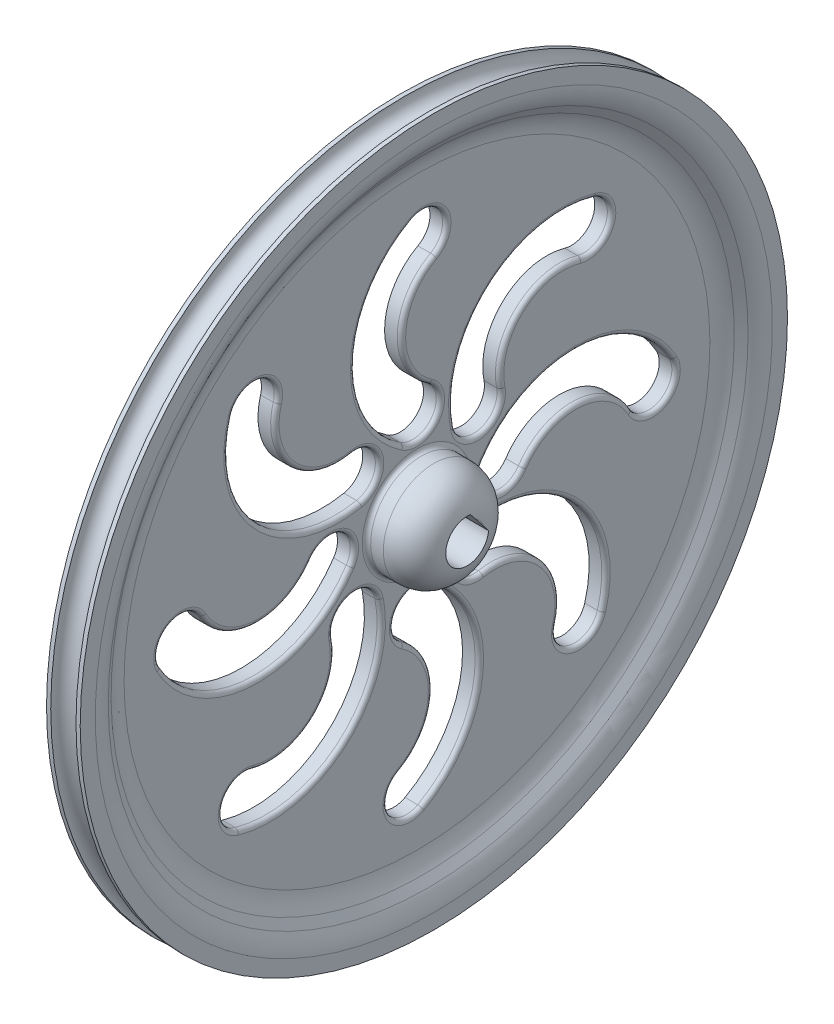
SolidWorks part; units mm, degrees
ref_plane "Płaszczyzna przednia" through (0, 0, 0) normal (0, 0, 1) x (1, 0, 0)
ref_plane "Płaszczyzna górna" through (0, 0, 0) normal (0, 1, 0) x (1, 0, 0)
ref_plane "Płaszczyzna prawa" through (0, 0, 0) normal (1, 0, 0) x (0, 0, -1)
sketch "Szkic1" plane through (0, 0, 0) normal (0, 0, 1) x (1, 0, 0)
  line L0 (6, -12.7789) -> (-2, -12.7789)
  line L1 (6, -12.7789) -> (6, -6.7789)
  line L2 (6, -6.7789) -> (0, -6.7789)
  line L3 (0, -6.7789) -> (0, 22.01)
  line L4 (2, 29.2211) -> (1.5, 29.2211)
  line L5 (2, 29.2211) -> (2, 27.4322)
  line L6 (-1.5, 29.2211) -> (-2, 29.2211)
  line L9 (-2, 29.2211) -> (-2, -12.7789)
  line L10 (0.6718, 24.2288) -> (1.3282, 25.2134)
  arc A0 (1.5, 29.2211) -> (-1.5, 29.2211) centre (0, 29.2211) cw
  arc A1 (2, 27.4322) -> (1.3282, 25.2134) centre (-2, 27.4322) cw
  arc A2 (0, 22.01) -> (0.6718, 24.2288) centre (4, 22.01) cw
  point P10 (2, 26.2211)
  point P17 (0, 23.2211)
  dimension "D6" = 1.5
  dimension "D9" = 4
  dimension "D10" = 4
  dimension "D1" = 8
  dimension "D2" = 6
  dimension "D3" = 42
  dimension "D4" = 4
  dimension "D5" = 3
  dimension "D7" = 0.5
  dimension "D8" = 30
  dimension "D11" = 2
revolve "Obrót1" add sketch "Szkic1" angle 360 about L0
sketch "Szkic4" plane through (6, 0, 0) normal (1, 0, 0) x (0, 0, -1)
  line L0 (0.3809, -10.2575) -> (2.5412, -12.9904)
  arc A0 (0.3809, -10.2575) -> (2.5412, -12.9904) centre (0, -12.7789) ccw
  circle A2 centre (0, -12.7789) radius 6 construction
extrude "Wytnij-wyciągnięcie8" cut sketch "Szkic4" against normal through all
sketch "Szkic5" plane through (0, 0, 0) normal (1, 0, 0) x (0, 0, -1)
  arc A0 (0.7629, 14.985) -> (0, -2.7789) centre (5.766, 5.8718) ccw construction
  arc A1 (-0.5757, 17.4232) -> (-1.5427, -5.0934) centre (5.766, 5.8718) ccw
  arc A2 (2.1015, 12.5467) -> (1.5427, -0.4644) centre (5.766, 5.8718) ccw
  arc A3 (2.1015, 12.5467) -> (-0.5757, 17.4232) centre (0.7629, 14.985) ccw
  arc A4 (-1.5427, -5.0934) -> (1.5427, -0.4644) centre (0, -2.7789) ccw
  circle A5 centre (0, -12.7789) radius 6 construction
  circle A6 centre (0, -12.7789) radius 34.7889 construction
  arc A7 (20.3278, 6.2489) -> (7.2274, -5.7726) centre (17.4216, -3.7328) ccw construction
  arc A8 (21.1053, 8.9195) -> (4.5, -6.3183) centre (17.4216, -3.7328) ccw
  arc A9 (19.5502, 3.5783) -> (9.9548, -5.2269) centre (17.4216, -3.7328) ccw
  arc A10 (19.5502, 3.5783) -> (21.1053, 8.9195) centre (20.3278, 6.2489) ccw
  arc A11 (4.5, -6.3183) -> (9.9548, -5.2269) centre (7.2274, -5.7726) ccw
  arc A12 (27.985, -13.7629) -> (10.2211, -13) centre (18.8718, -18.766) ccw construction
  arc A13 (30.4232, -12.4243) -> (7.9066, -11.4573) centre (18.8718, -18.766) ccw
  arc A14 (25.5467, -15.1015) -> (12.5356, -14.5427) centre (18.8718, -18.766) ccw
  arc A15 (25.5467, -15.1015) -> (30.4232, -12.4243) centre (27.985, -13.7629) ccw
  arc A16 (7.9066, -11.4573) -> (12.5356, -14.5427) centre (10.2211, -13) ccw
  arc A17 (19.2489, -33.3278) -> (7.2274, -20.2274) centre (9.2672, -30.4216) ccw construction
  arc A18 (21.9195, -34.1053) -> (6.6817, -17.5) centre (9.2672, -30.4216) ccw
  arc A19 (16.5783, -32.5502) -> (7.7731, -22.9548) centre (9.2672, -30.4216) ccw
  arc A20 (16.5783, -32.5502) -> (21.9195, -34.1053) centre (19.2489, -33.3278) ccw
  arc A21 (6.6817, -17.5) -> (7.7731, -22.9548) centre (7.2274, -20.2274) ccw
  arc A22 (-0.7629, -40.985) -> (0, -23.2211) centre (-5.766, -31.8718) ccw construction
  arc A23 (0.5757, -43.4232) -> (1.5427, -20.9066) centre (-5.766, -31.8718) ccw
  arc A24 (-2.1015, -38.5467) -> (-1.5427, -25.5356) centre (-5.766, -31.8718) ccw
  arc A25 (-2.1015, -38.5467) -> (0.5757, -43.4232) centre (-0.7629, -40.985) ccw
  arc A26 (1.5427, -20.9066) -> (-1.5427, -25.5356) centre (0, -23.2211) ccw
  arc A27 (-20.3278, -32.2489) -> (-7.2274, -20.2274) centre (-17.4216, -22.2672) ccw construction
  arc A28 (-21.1053, -34.9195) -> (-4.5, -19.6817) centre (-17.4216, -22.2672) ccw
  arc A29 (-19.5502, -29.5783) -> (-9.9548, -20.7731) centre (-17.4216, -22.2672) ccw
  arc A30 (-19.5502, -29.5783) -> (-21.1053, -34.9195) centre (-20.3278, -32.2489) ccw
  arc A31 (-4.5, -19.6817) -> (-9.9548, -20.7731) centre (-7.2274, -20.2274) ccw
  arc A32 (-27.985, -12.2371) -> (-10.2211, -13) centre (-18.8718, -7.234) ccw construction
  arc A33 (-30.4232, -13.5757) -> (-7.9066, -14.5427) centre (-18.8718, -7.234) ccw
  arc A34 (-25.5467, -10.8985) -> (-12.5356, -11.4573) centre (-18.8718, -7.234) ccw
  arc A35 (-25.5467, -10.8985) -> (-30.4232, -13.5757) centre (-27.985, -12.2371) ccw
  arc A36 (-7.9066, -14.5427) -> (-12.5356, -11.4573) centre (-10.2211, -13) ccw
  arc A37 (-19.2489, 7.3278) -> (-7.2274, -5.7726) centre (-9.2672, 4.4216) ccw construction
  arc A38 (-21.9195, 8.1053) -> (-6.6817, -8.5) centre (-9.2672, 4.4216) ccw
  arc A39 (-16.5783, 6.5502) -> (-7.7731, -3.0452) centre (-9.2672, 4.4216) ccw
  arc A40 (-16.5783, 6.5502) -> (-21.9195, 8.1053) centre (-19.2489, 7.3278) ccw
  arc A41 (-6.6817, -8.5) -> (-7.7731, -3.0452) centre (-7.2274, -5.7726) ccw
  point P3 (-4.6206, 6.3178)
  point P18 (10.3925, 3.9271)
  point P26 (19.3178, -8.3794)
  point P34 (16.9271, -23.3925)
  point P42 (4.6206, -32.3178)
  point P50 (-10.3925, -29.9271)
  point P58 (-19.3178, -17.6206)
  point P66 (-16.9271, -2.6075)
  point P71 (0, -13)
  dimension "D1" = 10
  dimension "D2" = 27.7744
  dimension "D3" = 8
extrude "Wytnij-wyciągnięcie9" cut sketch "Szkic5" against normal through all
fillet "Zaokrąglenie1" radius 4 1 edges at (6, -6.7789, 0)
fillet "Zaokrąglenie2" radius 0.5 33 edges at (0, -6.7789, 0) (0, 6.4372, 7.3996) (0, -4.3216, -2.3145) (0, 6.1985, 1.8417) (0, 16.3236, -3.2011) (0, 5.9765, -8.5119) (0, -8.5, -7.7731) (0, 1.8777, -12.2731) (0, 5.4714, -22.9984) (0, -5.6004, -19.4372) (0, -15.3145, -8.6784) (0, -11.1583, -19.1985) (0, -16.2011, -29.3236) (0, -21.5119, -18.9765) (0, -20.7731, -4.5) (0, -25.2731, -14.8777) (0, -35.9984, -18.4714) (0, -32.4372, -7.3996) (0, -21.6784, 2.3145) (0, -32.1985, -1.8417) (0, -42.3236, 3.2011) (0, -31.9765, 8.5119) (0, -17.5, 7.7731) (0, -27.8777, 12.2731) (0, -31.4714, 22.9984) (0, -20.3996, 19.4372) (0, -10.6855, 8.6784) (0, -14.8417, 19.1985) (0, -9.7989, 29.3236) (0, -4.4881, 18.9765) (0, -5.2269, 4.5) (0, -0.7269, 14.8777) (0, 9.9984, 18.4714)
